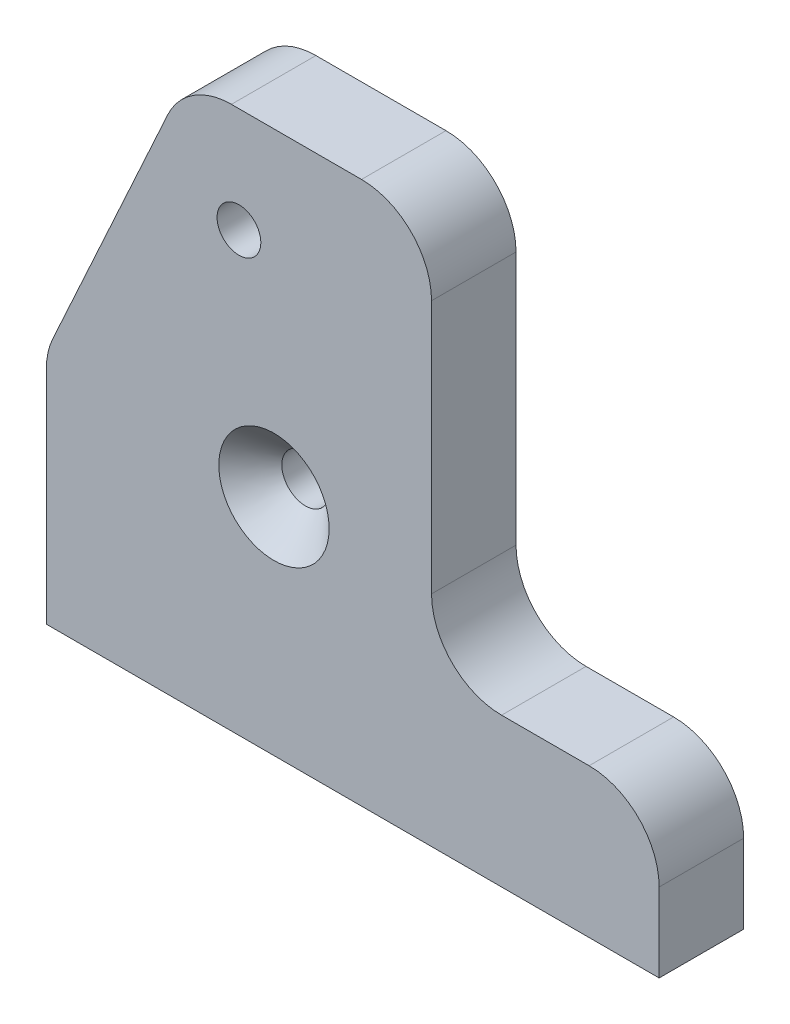
SolidWorks part; units mm, degrees
material "6061 Alloy"
ref_plane "Front" through (0, 0, 0) normal (0, 0, 1) x (1, 0, 0)
ref_plane "Top" through (0, 0, 0) normal (0, 1, 0) x (1, 0, 0)
ref_plane "Right" through (0, 0, 0) normal (1, 0, 0) x (0, 0, -1)
sketch "Sketch1" plane through (0, 0, 0) normal (0, 0, 1) x (1, 0, 0)
  line L0 (0, 0) -> (0, 13.5)
  line L9 (35, 0) -> (0, 0)
  line L15 (8, 31) -> (22, 31)
  line L16 (22, 31) -> (22, 8.5)
  line L17 (22, 8.5) -> (35, 8.5)
  line L18 (35, 8.5) -> (35, 0)
  line L22 (8, 31) -> (0, 13.5)
  dimension "D3" = 13.5
  dimension "D1" = 35
  dimension "D2" = 13
  dimension "D4" = 14
  dimension "D5" = 31
  dimension "D6" = 8.5
extrude "Boss-Extrude1" add sketch "Sketch1" along normal blind 4.826 contours L9 region at (14.4839, 12.8428, 0)
hole_wizard "M3x0.5 Tapped Hole2" positions "Sketch13" profile "Sketch14" tap size "M3x0.5" standard "ANSI Metric" end condition through all
sketch "Sketch13" plane through (0, 0, 4.826) normal (0, 0, 1) x (1, 0, 0)
  line L2 (35, 0) -> (0, 0) construction
  point P5 (11, 25)
  dimension "D1" = 25
  dimension "D2" = 11
sketch "Sketch14" plane through (11, 25, 4.826) normal (1, 0, 0) x (0, -1, 0)
  line L0 (0, 0) -> (0, 4.826)
  line L1 (0, 4.826) -> (1.25, 4.826)
  line L2 (1.25, 4.826) -> (1.25, 0)
  line L5 (1.25, 0) -> (0, 0)
  line L11 (0, -6.35) -> (0, 107.95) construction
  dimension "Thru Tap Drill Dia." = 2.5
  dimension "Thru Tap Drill Depth" = 4.826
cosmetic thread "Hole Thread1" parameters "D2"=3
sketch "Sketch16" plane through (0, 0, 0) normal (0, -1, 0) x (1, 0, 0)
  line L0 (0, 4.826) -> (0, 0) construction
  line L3 (0, 2.413) -> (42.6944, 2.413) construction
  point P0 (28.73, 2.413)
  point P1 (16.73, 2.413)
  dimension "D1" = 16.73
  dimension "D2" = 12
hole_wizard "M3x0.5 Tapped Hole3" positions "Sketch17" profile "Sketch18" tap size "M3x0.5" standard "ANSI Metric"
sketch "Sketch17" plane through (0, 0, 0) normal (0, -1, 0) x (-1, 0, 0)
  point P0 (-16.73, -2.413)
  point P3 (-28.73, -2.413)
sketch "Sketch18" plane through (16.73, 0, 2.413) normal (1, 0, 0) x (0, 0, -1)
  line L0 (0, 0) -> (0, 5.7511)
  line L1 (0, 5.7511) -> (1.25, 5)
  line L2 (1.25, 5) -> (1.25, 0)
  line L5 (1.25, 0) -> (0, 0)
  line L10 (0, 5.7511) -> (-1.25, 5) construction
  line L11 (0, -6.35) -> (0, 107.95) construction
  dimension "Tap Drill Dia." = 2.5
  dimension "Tap Drill Depth" = 5
  dimension "Drill Angle" = 118
chamfer "Chamfer1" [suppressed] distance 13 distance2 10
fillet "Fillet2" radius 4 5 edges at (35, 8.5, 2.413) (22, 8.5, 2.413) (22, 31, 2.413) (0, 13.5, 2.413) (8, 31, 2.413)
sketch "Sketch19" plane through (0, 0, 4.826) normal (0, 0, 1) x (1, 0, 0)
  line L0 (11, 25) -> (11, 12.8)
  line L1 (11, 12.8) -> (13, 12.8)
  circle A0 centre (13, 12.8) radius 1.25
  dimension "D3" = 2.5
  dimension "D1" = 12.2
  dimension "D2" = 2
extrude "Cut-Extrude1" cut sketch "Sketch19" against normal blind 10 contours A0 region at (13, 11.5854, 4.826)
hole_wizard "CSK for M3 Flat Head Machine Screw1" positions "Sketch20" profile "Sketch22" countersink size "M3" standard "ANSI Metric" end condition through all
sketch "Sketch20" plane through (0, 0, 4.826) normal (0, 0, 1) x (1, 0, 0)
  point P0 (13, 12.8)
sketch "Sketch22" plane through (13, 12.8, 4.826) normal (1, 0, 0) x (0, -1, 0)
  line L0 (0, 0) -> (0, 4.826)
  line L1 (0, 4.826) -> (1.35, 4.826)
  line L2 (1.35, 4.826) -> (1.35, 1.8)
  line L3 (1.35, 1.8) -> (3.15, 0)
  line L5 (3.15, 0) -> (0, 0)
  line L6 (-1.35, 1.8) -> (-3.15, 0) construction
  line L11 (0, -6.35) -> (0, 107.95) construction
  dimension "Thru Hole Dia." = 2.7
  dimension "Thru Hole Depth" = 4.826
  dimension "Near C'Sink Dia." = 6.3
  dimension "Near C'Sink Angle" = 90
